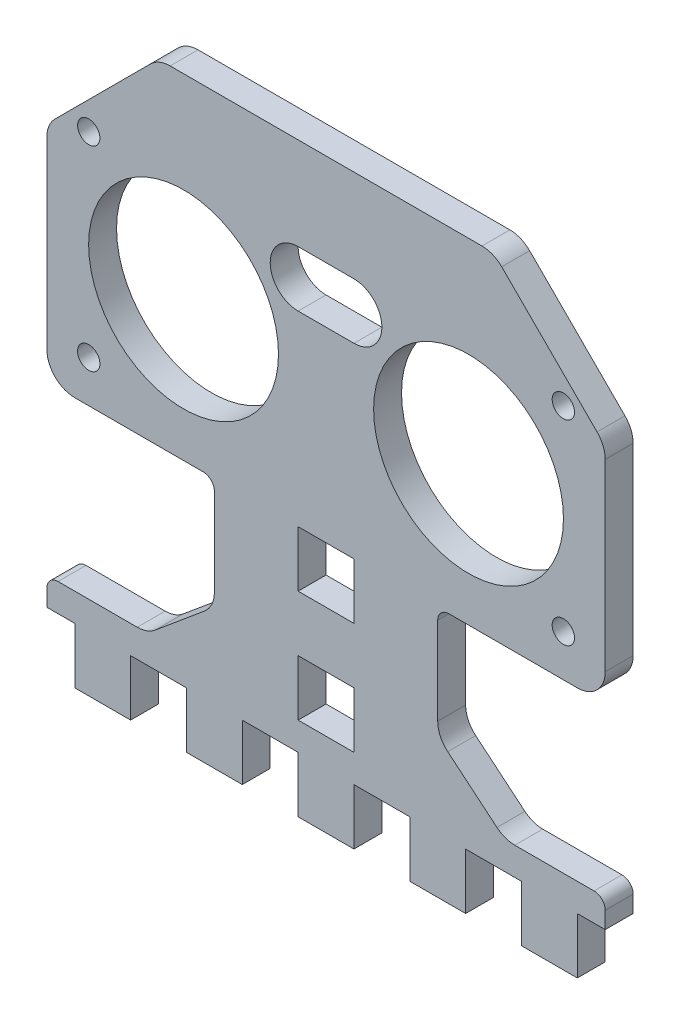
SolidWorks part; units mm, degrees
material "Maple"
ref_plane "Front" through (0, 0, 0) normal (0, 0, 1) x (1, 0, 0)
ref_plane "Top" through (0, 0, 0) normal (0, 1, 0) x (1, 0, 0)
ref_plane "Right" through (0, 0, 0) normal (1, 0, 0) x (0, 0, -1)
sketch "Sketch1" plane through (0, 0, 0) normal (0, 0, 1) x (1, 0, 0)
  line L0 (0, -6.5734) -> (0, 15.6465) construction
  line L1 (-22.5, -10) -> (22.5, -10) construction
  line L2 (-22.5, -10) -> (-22.5, 10) construction
  line L3 (-22.5, 10) -> (22.5, 10) construction
  line L4 (22.5, -10) -> (22.5, 10) construction
  line L5 (-22.5, -10) -> (22.5, 10) construction
  line L6 (-22.5, 10) -> (22.5, -10) construction
  line L7 (-25, -12.5) -> (25, -12.5) construction
  line L8 (-25, -12.5) -> (-25, 17.5) construction
  line L9 (-25, 17.5) -> (25, 17.5) construction
  line L10 (25, -12.5) -> (25, 17.5) construction
  line L11 (-25, -12.5) -> (25, 17.5) construction
  line L12 (-25, 17.5) -> (25, -12.5) construction
  line L13 (-13.9777, 0) -> (-4.3511, 0) construction
  line L14 (-10, -12.5) -> (-10, -22.5) construction
  line L15 (-10, -22.5) -> (-16, -27.5) construction
  line L16 (-16, -27.5) -> (-25, -27.5) construction
  line L17 (-25, -27.5) -> (-25, -35) construction
  line L18 (-25, -35) -> (25, -35) construction
  line L19 (-25, -30) -> (25, -30) construction
  line L20 (25, -27.5) -> (25, -35) construction
  line L21 (16, -27.5) -> (25, -27.5) construction
  line L22 (10, -22.5) -> (16, -27.5) construction
  line L23 (10, -12.5) -> (10, -22.5) construction
  line L24 (-10, -13.5) -> (-10, -21.3291)
  line L26 (-25, -10) -> (-25, 6.4645)
  line L27 (-13.9645, 17.5) -> (13.9645, 17.5)
  line L28 (25, -10) -> (25, 6.4645)
  line L29 (-25, -12.5) -> (25, 17.5) construction
  line L30 (-25, 17.5) -> (25, -12.5) construction
  line L31 (-10.8995, -23.2496) -> (-15.3047, -26.9206)
  line L32 (-16.9051, -27.5) -> (-24, -27.5)
  line L33 (-25, -27.5) -> (-25, -35) construction
  line L35 (-17.5, -35) -> (-17.5, -30)
  line L36 (-17.5, -30) -> (-12.5, -30)
  line L37 (-12.5, -30) -> (-12.5, -35)
  line L38 (-12.5, -35) -> (-7.5, -35)
  line L39 (-7.5, -35) -> (-7.5, -30)
  line L40 (-7.5, -30) -> (-2.5, -30)
  line L41 (-2.5, -30) -> (-2.5, -35)
  line L42 (-2.5, -35) -> (2.5, -35)
  line L43 (2.5, -30) -> (2.5, -35)
  line L44 (7.5, -30) -> (2.5, -30)
  line L45 (7.5, -35) -> (7.5, -30)
  line L46 (12.5, -35) -> (7.5, -35)
  line L47 (12.5, -30) -> (12.5, -35)
  line L48 (17.5, -30) -> (12.5, -30)
  line L49 (17.5, -35) -> (17.5, -30)
  line L51 (25, -35) -> (25, -28.5) construction
  line L52 (24, -27.5) -> (16.9051, -27.5)
  line L53 (15.3047, -26.9206) -> (10.8995, -23.2496)
  line L54 (10, -21.3291) -> (10, -13.5)
  line L55 (11, -12.5) -> (22.5, -12.5)
  line L56 (-2.5, -17.5) -> (-2.5, -12.5)
  line L57 (-2.5, -27.5) -> (2.5, -27.5)
  line L58 (-2.5, -27.5) -> (-2.5, -22.5)
  line L59 (-2.5, -22.5) -> (2.5, -22.5)
  line L60 (2.5, -27.5) -> (2.5, -22.5)
  line L61 (-2.5, -27.5) -> (2.5, -22.5) construction
  line L62 (-2.5, -22.5) -> (2.5, -27.5) construction
  line L63 (-2.5, -17.5) -> (2.5, -17.5)
  line L64 (2.5, -17.5) -> (2.5, -12.5)
  line L65 (-2.5, -12.5) -> (2.5, -12.5)
  line L66 (-24.2678, 8.2322) -> (-15.7322, 16.7678)
  line L71 (15.7322, 16.7678) -> (24.2678, 8.2322)
  line L72 (-22.5, -12.5) -> (-11, -12.5)
  line L73 (-5, 4.22) -> (5, 4.22)
  line L74 (-5, 4.22) -> (-5, 9.22)
  line L75 (-5, 9.22) -> (5, 9.22)
  line L76 (5, 4.22) -> (5, 9.22)
  line L77 (-5, 4.22) -> (5, 9.22) construction
  line L78 (-5, 9.22) -> (5, 4.22) construction
  line L79 (-25, -28.5) -> (-25, -35) construction
  line L80 (25, -30) -> (22.5, -30)
  line L81 (22.5, -30) -> (22.5, -35)
  line L82 (-25, -28.5) -> (-25, -30)
  line L83 (-25, -30) -> (-22.5, -30)
  line L84 (-22.5, -30) -> (-22.5, -35)
  line L85 (-22.5, -35) -> (-17.5, -35)
  line L86 (17.5, -35) -> (22.5, -35)
  line L87 (25, -30) -> (25, -28.5)
  circle A0 centre (12.76, 0) radius 8.5
  circle A1 centre (21.25, 8.75) radius 1
  circle A2 centre (-21.25, 8.75) radius 1
  circle A3 centre (-12.76, 0) radius 8.5
  circle A4 centre (21.25, -8.75) radius 1
  circle A5 centre (-21.25, -8.75) radius 1
  arc A6 (22.5, -12.5) -> (25, -10) centre (22.5, -10) ccw
  arc A7 (-22.5, -12.5) -> (-25, -10) centre (-22.5, -10) cw
  arc A8 (16.9051, -27.5) -> (15.3047, -26.9206) centre (16.9051, -25) cw
  arc A9 (10.8995, -23.2496) -> (10, -21.3291) centre (12.5, -21.3291) cw
  arc A10 (-15.3047, -26.9206) -> (-16.9051, -27.5) centre (-16.9051, -25) cw
  arc A11 (-10, -21.3291) -> (-10.8995, -23.2496) centre (-12.5, -21.3291) cw
  arc A12 (24.2678, 8.2322) -> (25, 6.4645) centre (22.5, 6.4645) cw
  arc A13 (15.7322, 16.7678) -> (13.9645, 17.5) centre (13.9645, 15) ccw
  arc A14 (-15.7322, 16.7678) -> (-13.9645, 17.5) centre (-13.9645, 15) cw
  arc A15 (-24.2678, 8.2322) -> (-25, 6.4645) centre (-22.5, 6.4645) ccw
  arc A16 (-24, -27.5) -> (-25, -28.5) centre (-24, -28.5) ccw
  arc A17 (25, -28.5) -> (24, -27.5) centre (24, -28.5) ccw
  arc A18 (10, -13.5) -> (11, -12.5) centre (11, -13.5) cw
  arc A19 (-10, -13.5) -> (-11, -12.5) centre (-11, -13.5) ccw
  point P0 (0, 0)
  point P6 (0, 2.5)
  point P23 (0, 2.5)
  point P25 (0, -30)
  point P26 (0, -35)
  point P40 (0, -35)
  point P47 (0, -25)
  point P73 (0, 6.72)
  point P97 (25, 7.5)
  point P100 (15, 17.5)
  point P103 (-15, 17.5)
  point P106 (-25, 7.5)
  point P123 (25, -31.25)
  point P124 (0, 0)
  point P125 (0, 0)
  dimension "D16" = 2
  dimension "D17" = 17
  dimension "D23" = 2.5
  dimension "D24" = 2.5
  dimension "D27" = 1
  dimension "D1" = 45
  dimension "D2" = 50
  dimension "D3" = 20
  dimension "D4" = 30
  dimension "D5" = 2.5
  dimension "D6" = 7.5
  dimension "D7" = 10
  dimension "D8" = 9
  dimension "D9" = 10
  dimension "D10" = 22.5
  dimension "D11" = 5
  dimension "D12" = 5
  dimension "D13" = 5
  dimension "D15" = 5
  dimension "D18" = 17.5
  dimension "D19" = 42.5
  dimension "D20" = 25.52
  dimension "D21" = 10
  dimension "D22" = 5
  dimension "D28" = 2.5
  dimension "D29" = 2.5
  dimension "D30" = 2.5
  dimension "D31" = 0.78
  dimension "D14" = 2
extrude "Boss-Extrude1" add sketch "Sketch1" along normal blind 2.5
fillet "Fillet1" 2 edges at (-5, 9.22, 1.25) (-5, 4.22, 1.25) type full round first side face at (0, 9.22, 1.25) second side face at (0, 4.22, 1.25) middle face at (-5, 6.72, 1.25)
fillet "Fillet2" 2 edges at (5, 9.22, 1.25) (5, 4.22, 1.25) type full round first side face at (1.25, 9.22, 1.25) second side face at (1.25, 4.22, 1.25) middle face at (5, 6.72, 1.25)
